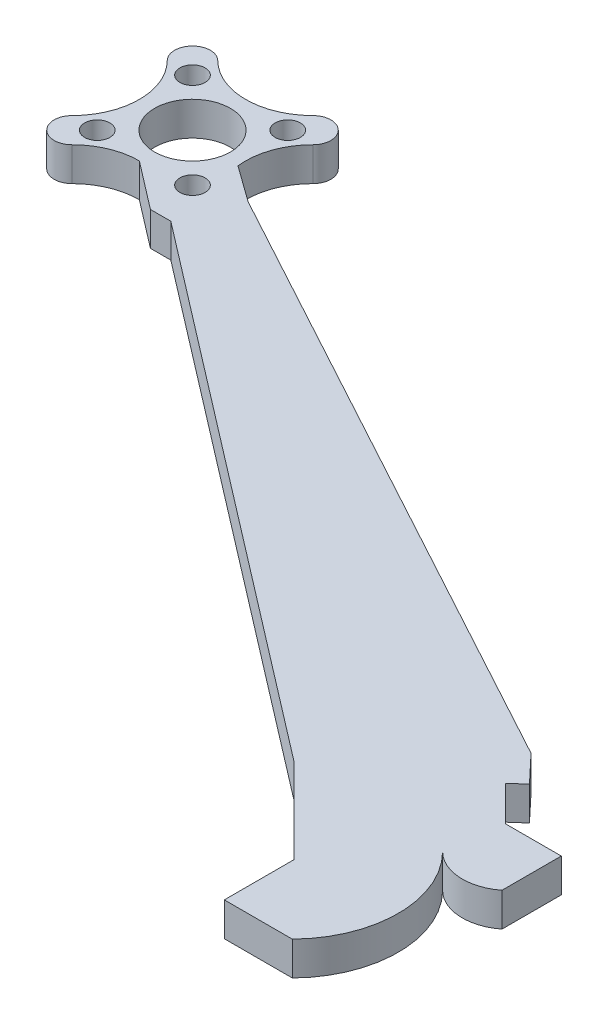
SolidWorks part; units mm, degrees
ref_plane "Front Plane" through (0, 0, 0) normal (0, 0, 1) x (1, 0, 0)
ref_plane "Top Plane" through (0, 0, 0) normal (0, 1, 0) x (1, 0, 0)
ref_plane "Right Plane" through (0, 0, 0) normal (1, 0, 0) x (0, 0, -1)
sketch "Sketch1" plane through (0, 0, 0) normal (0, 1, 0) x (1, 0, 0)
  line L1 (8.155, -8.155) -> (-8.155, -8.155)
  line L2 (8.155, -8.155) -> (8.155, 8.155)
  line L3 (8.155, 8.155) -> (-8.155, 8.155)
  line L4 (-8.155, -8.155) -> (-8.155, 8.155)
  line L5 (8.155, -8.155) -> (-8.155, 8.155) construction
  line L6 (8.155, 8.155) -> (-8.155, -8.155) construction
  circle A0 centre (0, 0) radius 4.5
  dimension "D1" = 9
  dimension "D2" = 16.31
  dimension "D3" = 16.31
extrude "Boss-Extrude1" add sketch "Sketch1" along normal blind 4
sketch "Sketch3" plane through (0, 4, 0) normal (0, 1, 0) x (1, 0, 0)
  line L0 (0, 0) -> (0, 8.155) construction
  line L1 (8.155, 8.155) -> (-8.155, 8.155) construction
  line L2 (0, 0) -> (-8.155, 0) construction
  line L3 (-8.155, 8.155) -> (-8.155, -8.155) construction
  line L4 (0, 0) -> (0, -8.155) construction
  line L5 (-8.155, -8.155) -> (8.155, -8.155) construction
  line L6 (0, 0) -> (8.155, 0) construction
  line L7 (8.155, -8.155) -> (8.155, 8.155) construction
  line L8 (0, 0) -> (5.6569, 5.6569) construction
  line L9 (0, 0) -> (5.6569, -5.6569) construction
  line L10 (0, 0) -> (-5.6569, -5.6569) construction
  line L11 (0, 0) -> (-5.6569, 5.6569) construction
  circle A0 centre (5.6569, 5.6569) radius 1.5
  circle A1 centre (5.6569, -5.6569) radius 1.5
  circle A2 centre (-5.6569, -5.6569) radius 1.5
  circle A3 centre (-5.6569, 5.6569) radius 1.5
  point P22 (0, 0)
  point P29 (0, 0)
  dimension "D2" = 3
  dimension "D1" = 4
  dimension "D3" = 4
extrude "Cut-Extrude1" cut sketch "Sketch3" against normal blind 4
sketch "Sketch4" plane through (0, 4, 0) normal (0, 1, 0) x (1, 0, 0)
  line L0 (8.155, -8.155) -> (0, -8.155)
  line L1 (-8.155, -8.155) -> (8.155, -8.155) construction
  line L2 (8.155, -8.155) -> (8.155, 0)
  line L3 (8.155, -8.155) -> (8.155, 8.155) construction
  line L4 (0, -8.155) -> (0, -10.655)
  line L5 (8.155, 0) -> (10.655, 0)
  line L6 (0, -10.655) -> (10.655, -10.655)
  line L7 (10.655, -10.655) -> (10.655, 0)
extrude "Boss-Extrude2" add sketch "Sketch4" against normal blind 4
sketch "Sketch9" plane through (0, 4, 0) normal (0, 1, 0) x (1, 0, 0)
  line L0 (71.0614, -58.9826) -> (7.5931, -10.2817)
  line L1 (84.1935, -43.9826) -> (10.6138, -4.0321)
  line L2 (71.0614, -58.9826) -> (81.0614, -68.9826)
  line L3 (7.5931, -10.2817) -> (10.6138, -4.0321)
  line L4 (81.0614, -68.9826) -> (81.0614, -73.9826)
  line L5 (81.0614, -73.9826) -> (96.0614, -73.9826)
  line L6 (96.0614, -73.9826) -> (96.0614, -50.291)
  line L7 (96.0614, -50.291) -> (90.502, -50.291)
  line L8 (90.502, -50.291) -> (84.1935, -43.9826)
extrude "Boss-Extrude6" add sketch "Sketch9" against normal blind 4
sketch "Sketch12" plane through (0, 4, 0) normal (0, 1, 0) x (1, 0, 0)
  line L0 (87.2786, -47.2583) -> (85.7805, -48.5833)
  line L1 (85.7805, -48.5833) -> (89.9609, -52.761)
  line L2 (89.9609, -52.761) -> (90.502, -52.761)
  line L3 (90.502, -52.761) -> (96.0614, -52.761)
  line L4 (96.0614, -52.761) -> (96.0614, -50.291)
  line L5 (87.3477, -47.1368) -> (90.502, -50.291)
  line L6 (90.502, -50.291) -> (96.0614, -50.291)
  line L7 (90.502, -50.291) -> (96.0614, -50.291)
  line L8 (87.2786, -47.2583) -> (87.3477, -47.1368)
extrude "Cut-Extrude3" cut sketch "Sketch12" against normal blind 4 contours L8 L5 L6 L4 L3 L2 L1 L0
sketch "Sketch13" plane through (0, 4, 0) normal (0, 1, 0) x (1, 0, 0)
  line L0 (81.0614, -73.9826) -> (81.0614, -77.2826)
  line L1 (96.0614, -52.761) -> (96.5614, -52.761)
  line L2 (81.0614, -73.9826) -> (96.0614, -73.9826)
  line L3 (96.0614, -73.9826) -> (96.0614, -52.761)
  line L4 (96.5614, -52.761) -> (96.5614, -77.2826)
  line L5 (81.0614, -77.2826) -> (96.5614, -77.2826)
  dimension "D1" = 3.3
  dimension "D2" = 0.5
extrude "Boss-Extrude7" add sketch "Sketch13" against normal blind 4
sketch "Sketch16" plane through (0, 4, 0) normal (0, 1, 0) x (1, 0, 0)
  line L0 (0, -10.655) -> (-10, -10.655)
  line L1 (-10, -10.655) -> (-10, 10.345)
  line L2 (10.655, 0) -> (10.655, 10.345)
  line L3 (10.655, 10.345) -> (-10, 10.345)
  line L4 (0, -10.655) -> (0, -8.155)
  line L5 (0, -8.155) -> (-8.155, -8.155)
  line L6 (-8.155, -8.155) -> (-8.155, 8.155)
  line L7 (-8.155, 8.155) -> (8.155, 8.155)
  line L8 (8.155, 8.155) -> (8.155, 0)
  line L9 (8.155, 0) -> (10.655, 0)
  dimension "D1" = 10
  dimension "D2" = 21
extrude "Boss-Extrude9" add sketch "Sketch16" against normal blind 4
sketch "Sketch17" plane through (0, 4, 0) normal (0, 1, 0) x (1, 0, 0)
  line L0 (-5.6569, 5.6569) -> (-5.6569, 8.6569) construction
  line L1 (-5.6569, 5.6569) -> (-8.6569, 5.6569) construction
  line L2 (5.6569, 5.6569) -> (5.6569, 8.6569) construction
  line L3 (5.6569, 5.6569) -> (8.6569, 5.6569) construction
  line L4 (-5.6569, -5.6569) -> (-8.6569, -5.6569) construction
  line L5 (-5.6569, -5.6569) -> (-5.6569, -8.6569) construction
  line L6 (5.6569, -5.6569) -> (8.6569, -5.6569) construction
  line L7 (5.6569, -5.6569) -> (5.6569, -8.6569) construction
  line L8 (5.6569, -8.6569) -> (5.6569, -10.655)
  line L9 (-10, -10.655) -> (8.0797, -10.655) construction
  line L10 (8.6569, -5.6569) -> (10.655, -4.0544)
  line L11 (5.6569, -10.655) -> (8.0797, -10.655)
  line L12 (8.0797, -10.655) -> (71.0614, -58.9826)
  line L13 (71.0614, -58.9826) -> (81.0614, -68.9826)
  line L14 (81.0614, -68.9826) -> (81.0614, -77.2826)
  line L15 (81.0614, -77.2826) -> (96.5614, -77.2826)
  line L16 (96.5614, -77.2826) -> (96.5614, -52.761)
  line L17 (96.5614, -52.761) -> (89.9609, -52.761)
  line L18 (89.9609, -52.761) -> (85.7805, -48.5833)
  line L19 (85.7805, -48.5833) -> (87.2786, -47.2583)
  line L20 (87.2786, -47.2583) -> (84.1935, -43.9826)
  line L21 (84.1935, -43.9826) -> (10.655, -4.0544)
  arc A0 (-5.6569, -8.6569) -> (5.6569, -8.6569) centre (0, -14.3137) cw
  arc A1 (8.6569, 5.6569) -> (8.6569, -5.6569) centre (14.3137, 0) ccw
  arc A2 (5.6569, 8.6569) -> (-5.6569, 8.6569) centre (0, 14.3137) cw
  arc A3 (-8.6569, 5.6569) -> (-8.6569, -5.6569) centre (-14.3137, 0) cw
  arc A4 (-8.6569, 5.6569) -> (-5.6569, 8.6569) centre (-7.1569, 7.1569) cw
  arc A5 (5.6569, 8.6569) -> (8.6569, 5.6569) centre (7.1569, 7.1569) cw
  arc A6 (-8.6569, -5.6569) -> (-5.6569, -8.6569) centre (-7.1569, -7.1569) ccw
  dimension "D1" = 3
  dimension "D2" = 3
  dimension "D3" = 3
  dimension "D4" = 3
extrude "Cut-Extrude4" cut sketch "Sketch17" against normal blind 4 flip side to cut
sketch "Sketch18" plane through (0, 4, 0) normal (0, 1, 0) x (1, 0, 0)
  line L0 (5.6569, -10.655) -> (0, -6.3137)
  line L1 (0, -6.3137) -> (6.3728, -0.9706)
  line L2 (6.3728, -0.9706) -> (10.655, -4.0544)
  line L3 (10.655, -4.0544) -> (8.6569, -5.6569)
  line L4 (8.6569, -5.6569) -> (5.6569, -10.655)
  arc A0 (5.6569, -8.6569) -> (-5.6569, -8.6569) centre (0, -14.3137) ccw construction
  arc A1 (8.6569, 5.6569) -> (8.6569, -5.6569) centre (14.3137, 0) ccw construction
  circle A2 centre (5.6569, -5.6569) radius 1.5
extrude "Boss-Extrude10" add sketch "Sketch18" against normal blind 4
sketch "Sketch19" plane through (0, 4, 0) normal (0, 1, 0) x (1, 0, 0)
  line L0 (96.5614, -52.761) -> (97.0614, -52.761)
  line L1 (96.5614, -77.2826) -> (99.0224, -77.6438)
  line L2 (96.5614, -77.2826) -> (96.5614, -52.761)
  line L3 (97.0614, -52.761) -> (97.0614, -77.356)
  line L4 (97.0614, -77.356) -> (97.0614, -59.356)
  line L5 (97.0614, -77.356) -> (89.0614, -77.356)
  arc A0 (89.0614, -59.356) -> (89.0614, -77.356) centre (80.0614, -68.356) cw
  arc A1 (89.0614, -59.356) -> (97.0614, -59.356) centre (93.0614, -55.356) ccw
  dimension "D1" = 0.5
  dimension "D2" = 98.35
extrude "Cut-Extrude5" cut sketch "Sketch19" against normal blind 4 contours L4 A1 A0 L5
